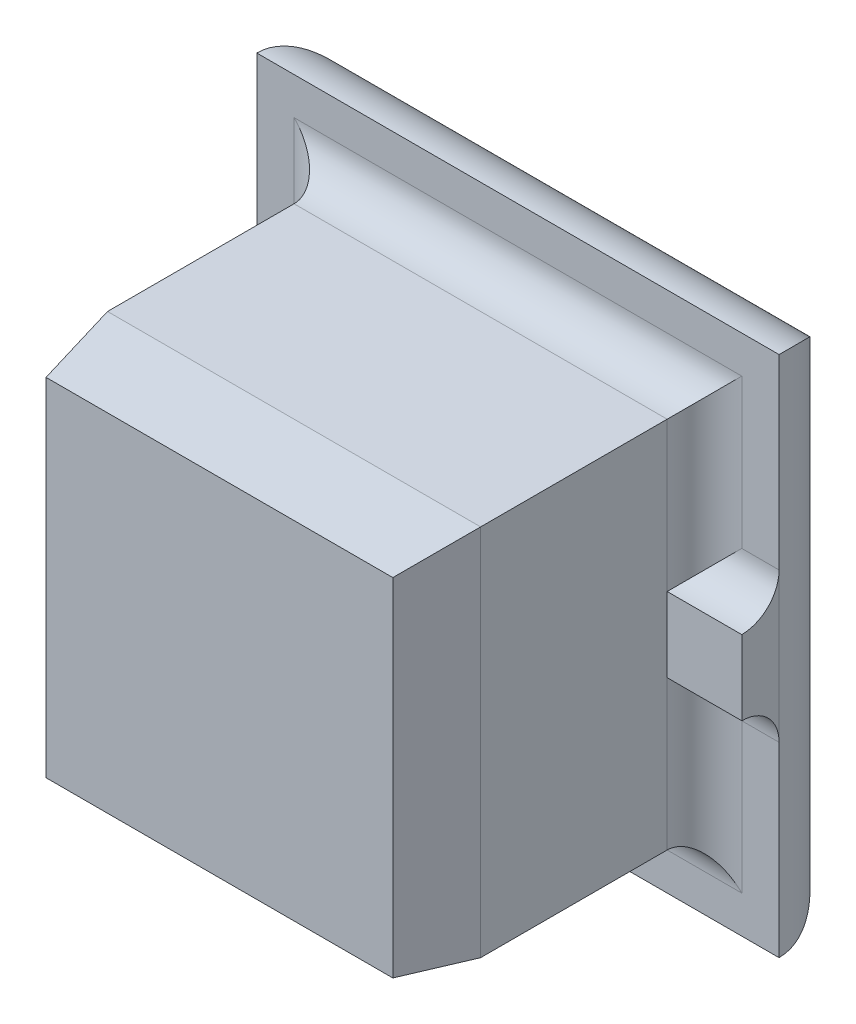
SolidWorks part; units mm, degrees
ref_plane "Front Plane" through (0, 0, 0) normal (0, 0, 1) x (1, 0, 0)
ref_plane "Top Plane" through (0, 0, 0) normal (0, 1, 0) x (1, 0, 0)
ref_plane "Right Plane" through (0, 0, 0) normal (1, 0, 0) x (0, 0, -1)
sketch "Sketch1" plane through (0, 0, 0) normal (0, 0, 1) x (1, 0, 0)
  line L1 (5, -5) -> (-5, -5)
  line L2 (5, -5) -> (5, 5)
  line L3 (5, 5) -> (-5, 5)
  line L4 (-5, -5) -> (-5, 5)
  line L5 (5, -5) -> (-5, 5) construction
  line L6 (5, 5) -> (-5, -5) construction
  point P0 (0, 0)
  dimension "D1" = 10
  dimension "D2" = 10
extrude "Boss-Extrude1" add sketch "Sketch1" along normal blind 8
sketch "Sketch2" plane through (0, 0, 0) normal (0, 0, -1) x (-1, 0, 0)
  line L0 (-5, 5) -> (5, 5) construction
  line L1 (7, -7) -> (-7, -7)
  line L2 (7, -7) -> (7, 7)
  line L3 (7, 7) -> (-7, 7)
  line L4 (-7, -7) -> (-7, 7)
  line L5 (7, -7) -> (-7, 7) construction
  line L6 (7, 7) -> (-7, -7) construction
  line L7 (5, 5) -> (5, -5) construction
  point P0 (0, 0)
  dimension "D1" = 2
  dimension "D2" = 2
extrude "Boss-Extrude2" add sketch "Sketch2" along normal blind 2
fillet "Fillet1" radius 2 4 edges at (0, 7, -2) (-7, 0, -2) (0, -7, -2) (7, 0, -2)
chamfer "Chamfer1" distance 2 angle 10 4 edges at (0, -5, 8) (5, 0, 8) (0, 5, 8) (-5, 0, 8) first distance on face at (0, -5, 4) first distance on face at (5, 0, 4) first distance on face at (0, 5, 4) first distance on face at (-5, 0, 4)
sketch "Sketch3" plane through (0, 0, 0) normal (0, 0, 1) x (1, 0, 0)
  line L0 (5, 5) -> (5, -5) construction
  line L1 (-7, 1) -> (-5, 1)
  line L2 (-7, 1) -> (-7, -1)
  line L3 (-7, -1) -> (-5, -1)
  line L4 (-5, 1) -> (-5, -1)
  line L5 (-7, 1) -> (-5, -1) construction
  line L6 (-7, -1) -> (-5, 1) construction
  line L7 (5, 1) -> (7, 1)
  line L8 (5, 1) -> (5, -1)
  line L9 (5, -1) -> (7, -1)
  line L10 (7, 1) -> (7, -1)
  line L11 (5, 1) -> (7, -1) construction
  line L12 (5, -1) -> (7, 1) construction
  line L13 (-5, 5) -> (-5, -5) construction
  point P0 (-6, 0)
  point P5 (6, 0)
  dimension "D1" = 2
  dimension "D2" = 2
  dimension "D3" = 2
  dimension "D4" = 2
extrude "Boss-Extrude3" add sketch "Sketch3" along normal blind 1
fillet "Fillet2" radius 1 10 edges at (6, 1, 0) (6, -1, 0) (-6, -1, 0) (-6, 1, 0) (5, 3, 0) (5, -3, 0) (-5, 3, 0) (-5, -3, 0) (0, 5, 0) (0, -5, 0)
